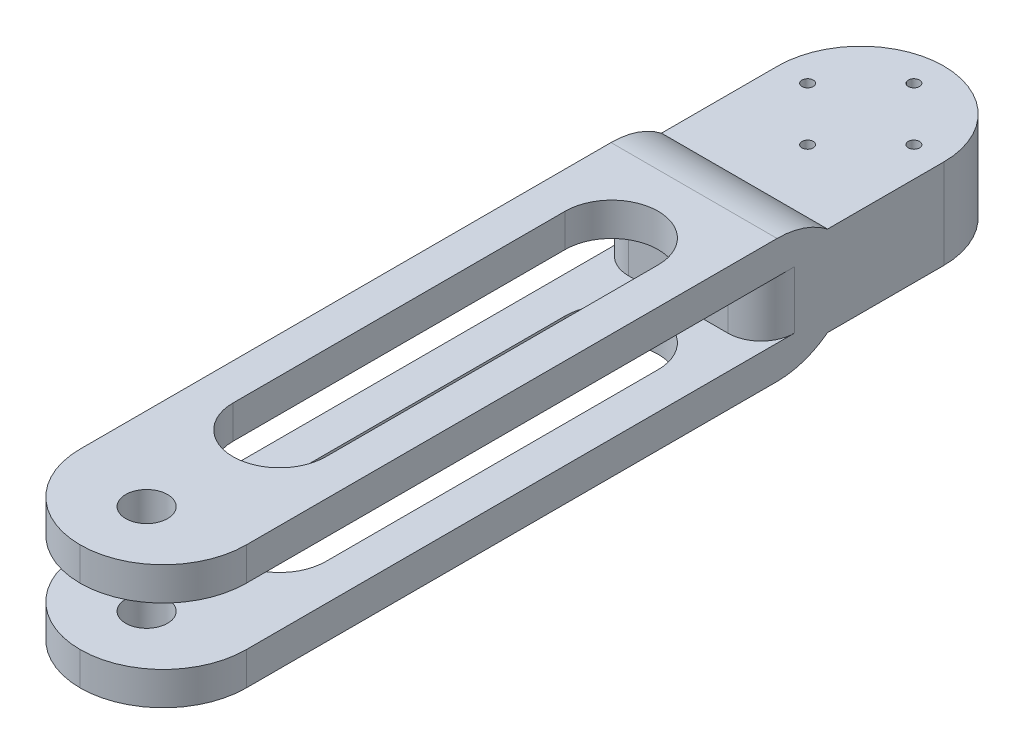
SolidWorks part; units mm, degrees
ref_plane "Plan de face" through (0, 0, 0) normal (0, 0, 1) x (1, 0, 0)
ref_plane "Plan de dessus" through (0, 0, 0) normal (0, 1, 0) x (1, 0, 0)
ref_plane "Plan de droite" through (0, 0, 0) normal (1, 0, 0) x (0, 0, -1)
sketch "Esquisse1" plane through (0, 0, 0) normal (1, 0, 0) x (0, 0, -1)
  line L0 (90, 9.325) -> (-10, 9.325)
  line L1 (-10, 9.325) -> (-10, 4.325)
  line L2 (90, 9.325) -> (90, 6.75)
  line L3 (90, 6.75) -> (120, 6.75)
  line L4 (-10, 4.325) -> (80, 4.325)
  line L5 (80, 4.325) -> (80, -4.325)
  line L6 (120, 6.75) -> (120, -6.75)
  line L7 (55, 0) -> (-55, 0) construction
  line L8 (-10, -4.325) -> (80, -4.325)
  line L9 (90, -6.75) -> (120, -6.75)
  line L10 (90, -9.325) -> (90, -6.75)
  line L11 (-10, -9.325) -> (-10, -4.325)
  line L12 (90, -9.325) -> (-10, -9.325)
  point P12 (120, 0)
  point P13 (80, 0)
  dimension "D1" = 130
  dimension "10" = 8.65
  dimension "D2" = 13.5
  dimension "D3" = 5
  dimension "D4" = 10
  dimension "D5" = 10
  dimension "D6" = 80
extrude "Boss.-Extru.1" add sketch "Esquisse1" along normal mid plane 25
fillet "Congé1" radius 12.5 8 edges at (0, -9.325, -90) (0, 9.325, -90) (-12.5, -6.825, 10) (-12.5, 6.825, 10) (12.5, -6.825, 10) (12.5, 6.825, 10) (-12.5, 0, -120) (12.5, 0, -120)
sketch "Esquisse2" plane through (0, 6.75, 0) normal (0, 1, 0) x (1, 0, 0)
  line L0 (-12.5, 107.5) -> (12.5, 107.5) construction
  line L1 (0, 120) -> (0, 226.6844) construction
  arc A0 (0, 120) -> (-12.5, 107.5) centre (0, 107.5) ccw construction
  circle A1 centre (8, 107.5) radius 0.85
  circle A2 centre (0, 115.5) radius 0.85
  circle A3 centre (-8, 107.5) radius 0.85
  circle A4 centre (0, 99.5) radius 0.85
  point P12 (0, 173.3422)
  dimension "D1" = 1.7
  dimension "D2" = 1.7
  dimension "D3" = 8
  dimension "D4" = 8
extrude "Enlèv. mat.-Extru.1" cut sketch "Esquisse2" against normal through all
sketch "Esquisse3" plane through (0, 9.325, 0) normal (0, 1, 0) x (1, 0, 0)
  circle A0 centre (0, 0) radius 3.15
  dimension "D1" = 6.3
extrude "Enlèv. mat.-Extru.2" cut sketch "Esquisse3" against normal through all
sketch "Esquisse4" plane through (0, 9.325, 0) normal (0, 1, 0) x (1, 0, 0)
  line L0 (-7, 70) -> (-7, 20)
  line L1 (0, -55) -> (0, 55) construction
  line L2 (7, 70) -> (7, 20)
  arc A0 (-7, 20) -> (7, 20) centre (0, 20) ccw
  arc A1 (-7, 70) -> (7, 70) centre (0, 70) cw
  dimension "D1" = 7
  dimension "D2" = 20
  dimension "D3" = 70
extrude "Enlèv. mat.-Extru.3" cut sketch "Esquisse4" against normal through all
fillet "Congé2" radius 5 2 edges at (-12.5, 0, -80) (12.5, 0, -80)
